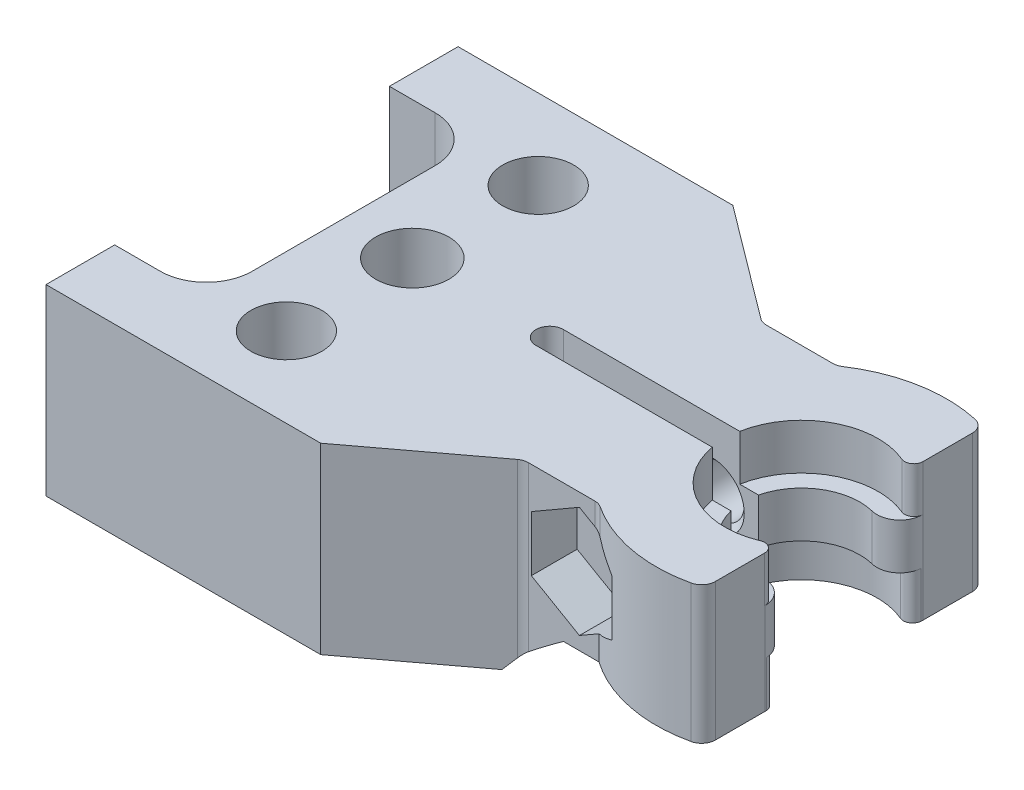
SolidWorks part; units mm, degrees
ref_plane "Front Plane" through (0, 0, 0) normal (0, 0, 1) x (1, 0, 0)
ref_plane "Top Plane" through (0, 0, 0) normal (0, 1, 0) x (1, 0, 0)
ref_plane "Right Plane" through (0, 0, 0) normal (1, 0, 0) x (0, 0, -1)
sketch "Sketch1" plane through (0, 0, 0) normal (0, 0, 1) x (1, 0, 0)
  line L0 (-3.35, 34) -> (-3.35, 32)
  line L1 (-3.35, 32) -> (-2.55, 32)
  line L2 (-2.55, 32) -> (-2.55, 30)
  line L3 (-2.55, 30) -> (-3.3, 30)
  line L4 (-3.3, 30) -> (-3.3, 28)
  line L5 (-3.3, 28) -> (-6.35, 28)
  line L6 (-6.35, 28) -> (-6.35, 34)
  line L7 (-6.35, 34) -> (-3.35, 34)
  line L8 (0, 0) -> (0, 43.3729) construction
  line L9 (-4.85, 34) -> (-4.85, 28) construction
  point P11 (-4.85, 34)
  point P12 (-3.3, 29)
  point P13 (-2.55, 31)
  point P14 (-4.85, 31)
  point P15 (0, 0)
  point P18 (-4.8, 35.6827)
  point P19 (-4.8, 29.6827)
  point P20 (0, 0)
  dimension "D1" = 6
  dimension "D2" = 2
  dimension "D3" = 3.35
  dimension "D4" = 3.3
  dimension "D5" = 2.55
  dimension "D6" = 30
  dimension "D8" = 3
revolve "Revolve1" add sketch "Sketch1" angle 360 about L8
sketch "Sketch2" plane through (0, 34, 0) normal (0, 1, 0) x (1, 0, 0)
  line L0 (-20, 9) -> (-12, 9)
  line L1 (-20, -9) -> (-12, -9)
  line L2 (-20, -9) -> (-20, 9)
  line L3 (0, 0) -> (-12, 9)
  line L4 (0, 0) -> (-12, -9)
  line L6 (-20, 9) -> (-24, 9)
  line L7 (-20, 9) -> (-20, 6)
  line L8 (-20, 6) -> (-24, 6)
  line L9 (-24, 9) -> (-24, 6)
  line L10 (-20, -9) -> (-24, -9)
  line L11 (-20, -9) -> (-20, -6)
  line L12 (-20, -6) -> (-24, -6)
  line L13 (-24, -9) -> (-24, -6)
  line L14 (-8.9905, 5.2) -> (-0.8022, 5.2)
  line L15 (-8.9905, 5.2) -> (-8.9905, -5.2)
  line L16 (-8.9905, -5.2) -> (-0.8022, -5.2)
  line L17 (-0.8022, 5.2) -> (-0.8022, -5.2)
  circle A0 centre (-17, 0) radius 1.6
  circle A1 centre (-17, 5.5) radius 1.55
  circle A2 centre (-17, -5.5) radius 1.55
  circle A3 centre (0, 0) radius 4.3057
  circle M1 centre (0, 0) radius 6.35
  dimension "D2" = 3.2
  dimension "D5" = 3.1
  dimension "D6" = 3.1
  dimension "D1" = 17
  dimension "D3" = 5.5
  dimension "D4" = 5.5
  dimension "D7" = 3
  dimension "D8" = 9
  dimension "D9" = 9
  dimension "D10" = 24
  dimension "D11" = 3
  dimension "D12" = 3
  dimension "D13" = 5.2
  dimension "D14" = 5.2
  dimension "D15" = 8
extrude "Boss-Extrude1" add sketch "Sketch2" against normal blind 8 contours L6 L9 L8 L2 | L13 L10 L2 L12 | L16 L15 L14 L3 L0 L2 L1 L4 A2 A1 A0 | L15 L16 L4 L3 L14 M1 | L14 L3 M1 | L4 L16 M1
sketch "Sketch3" plane through (0, 0, 0) normal (0, 1, 0) x (1, 0, 0)
  line L1 (10.087, 10.1783) -> (1.85, 10.1783)
  line L2 (10.087, 10.1783) -> (10.087, -10.4323)
  line L3 (10.087, -10.4323) -> (1.85, -10.4323)
  line L4 (1.85, 10.1783) -> (1.85, -10.4323)
  dimension "D1" = 1.85
extrude "Cut-Extrude1" cut sketch "Sketch3" along normal through all
chamfer "Chamfer1" distance 3 angle 45 2 edges at (-6.35, 28, 0) (-6.35, 26, 0)
fillet "Fillet4" radius 1 2 edges at (1.85, 31, 1.755) (1.85, 31, -1.755)
fillet "Fillet5" radius 0.4 4 edges at (1.6845, 33, -2.8957) (1.6558, 29, -2.8545) (1.6558, 29, 2.8545) (1.6845, 33, 2.8957)
fillet "Fillet6" radius 2 2 edges at (-20, 30, 6) (-20, 30, -6)
sketch "Sketch5" plane through (0, 0, 0) normal (0, 1, 0) x (1, 0, 0)
  line L0 (0, 0) -> (-11, 0) construction
  line L1 (0, -0.6) -> (-11, -0.6)
  line L2 (0, 0.6) -> (-11, 0.6)
  arc A0 (0, -0.6) -> (0, 0.6) centre (0, 0) ccw
  arc A1 (-11, 0.6) -> (-11, -0.6) centre (-11, 0) ccw
  point P3 (-5.5, 0)
  dimension "D1" = 11
extrude "Cut-Extrude2" cut sketch "Sketch5" along normal through all
sketch "Sketch7" plane through (0, 26, 0) normal (0, -1, 0) x (1, 0, 0)
  circle A0 centre (-17, 0) radius 1.6
  circle A1 centre (-17, 0) radius 2.5
extrude "Boss-Extrude2" add sketch "Sketch7" along normal blind 0.5
chamfer "Chamfer2" distance 0.5 angle 45 1 edges at (-17, 26, 2.5)
sketch "Sketch8" plane through (0, 0, 0) normal (0, 0, 1) x (1, 0, 0)
  line L1 (-4.5, 34) -> (-4.5, 28) construction
  line L2 (-6.9333, 34) -> (-3.6445, 34) construction
  line L3 (-5.1945, 28) -> (-3.6445, 28) construction
  circle A0 centre (-4.5, 31) radius 1.1
  point P9 (-4.5, 31)
  dimension "D3" = 2.2
  dimension "D1" = 4.5
extrude "Cut-Extrude4" cut sketch "Sketch8" against normal through all and the other way through all
fillet "Fillet7" radius 0.6 8 edges at (-3.6445, 32.8457, 5.2) (-3.6445, 32.8457, -5.2) (-3.4035, 31.0879, 5.3608) (1.85, 31, 6.0745) (1.85, 31, -6.0745) (-6.9333, 30.3417, 5.2) (-6.9333, 30.3417, -5.2)
sketch "Sketch9" plane through (0, 0, 5.2) normal (0, 0, 1) x (1, 0, 0)
  line L1 (-6.1168, 35) -> (-3.0969, 35)
  line L2 (-6.1168, 35) -> (-6.1168, 28)
  line L3 (-6.1168, 28) -> (-3.0969, 28)
  line L4 (-3.0969, 35) -> (-3.0969, 28)
  line L5 (-5.1945, 28) -> (-3.6445, 28) construction
  circle A0 centre (-4.5, 31) radius 1.1 construction
  circle A1 centre (-4.5, 31) radius 1.1
chamfer "Chamfer3" distance 0.3 angle 45 2 edges at (-3.4, 31, -0.6) (-5.6, 31, 0.6)
sketch "Sketch10" plane through (0, 0, 5.2) normal (0, 0, 1) x (1, 0, 0)
  line L1 (-4.5, 28.5751) -> (-2.4, 29.7876)
  line L2 (-2.4, 29.7876) -> (-2.4, 32.2124)
  line L3 (-2.4, 32.2124) -> (-4.5, 33.4249)
  line L4 (-4.5, 33.4249) -> (-6.6, 32.2124)
  line L5 (-6.6, 32.2124) -> (-6.6, 29.7876)
  line L6 (-6.6, 29.7876) -> (-4.5, 28.5751)
  circle A0 centre (-4.5, 31) radius 2.1 construction
  circle A1 centre (-4.5, 31) radius 1.1 construction
  point P11 (0, 0)
  dimension "D1" = 4.2
extrude "Cut-Extrude5" cut sketch "Sketch10" against normal blind 2 and the other way blind 1.2
sketch "Sketch11" plane through (0, 0, -5.2) normal (0, 0, -1) x (-1, 0, 0)
  circle A0 centre (4.5, 31) radius 1.95
  dimension "D1" = 3.9
extrude "Cut-Extrude6" cut sketch "Sketch11" against normal blind 2 and the other way blind 10
ref_plane "Plane1" through (0, 31, 0) normal (0, 1, 0) x (1, 0, 0)
